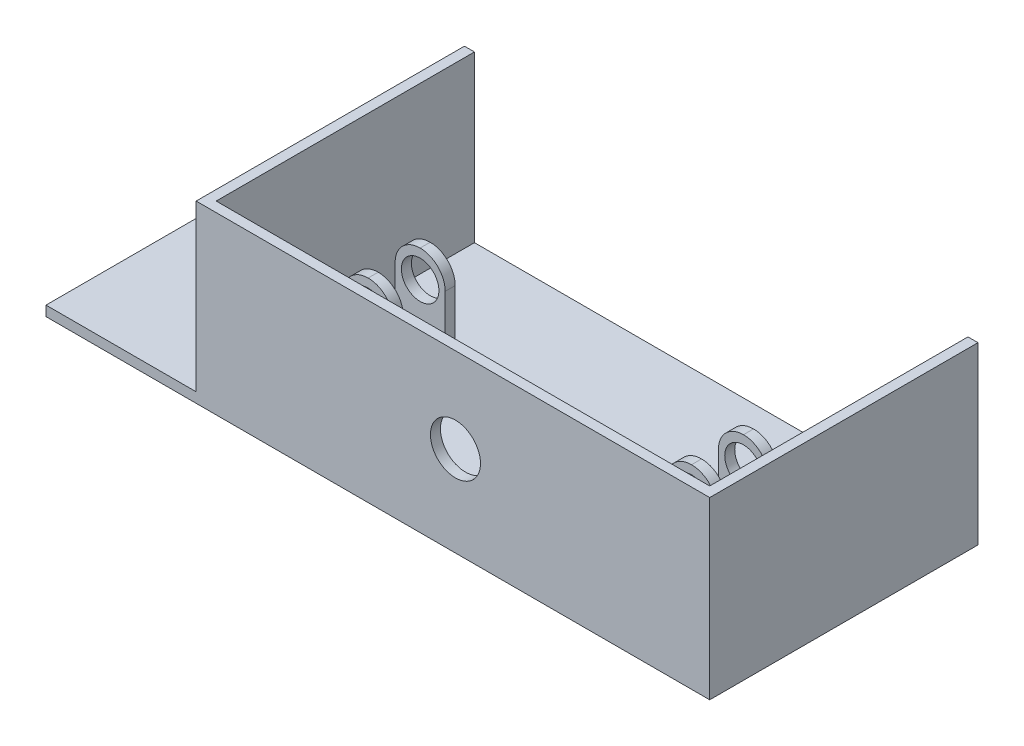
SolidWorks part; units mm, degrees
ref_plane "Plan de face" through (0, 0, 0) normal (0, 0, 1) x (1, 0, 0)
ref_plane "Plan de dessus" through (0, 0, 0) normal (0, 1, 0) x (1, 0, 0)
ref_plane "Plan de droite" through (0, 0, 0) normal (1, 0, 0) x (0, 0, -1)
sketch "Esquisse1" plane through (0, 0, 0) normal (0, 0, 1) x (1, 0, 0)
  line L1 (-17.4678, 19.1867) -> (85.1322, 19.1867)
  line L2 (-17.4678, 19.1867) -> (-17.4678, -15.8133)
  line L3 (-17.4678, -15.8133) -> (85.1322, -15.8133)
  line L4 (85.1322, 19.1867) -> (85.1322, -15.8133)
  dimension "D1" = 35
  dimension "D2" = 102.6
extrude "Boss.-Extru.1" add sketch "Esquisse1" along normal blind 53.6 and the other way blind 0.0001
sketch "Esquisse4" plane through (0, 19.1867, 0) normal (0, 1, 0) x (1, 0, 0)
  line L1 (-15.4678, -51.5999) -> (83.1322, -51.5999)
  line L2 (-15.4678, -51.5999) -> (-15.4678, 0.0001)
  line L3 (-15.4678, 0.0001) -> (83.1322, 0.0001)
  line L4 (83.1322, -51.5999) -> (83.1322, 0.0001)
  line L5 (-17.4678, -53.6) -> (-17.4678, 0.0001) construction
  line L6 (85.1322, -53.6) -> (85.1322, 0.0001) construction
  line L7 (85.1322, 0.0001) -> (-17.4678, 0.0001) construction
  dimension "D1" = 51.6
  dimension "D2" = 98.6
  dimension "D3" = 0
  dimension "D4" = 2
  dimension "D5" = 2
extrude "Enlèv. mat.-Extru.2" cut sketch "Esquisse4" against normal blind 33
sketch "Esquisse9" plane through (0, -13.8133, 0) normal (0, 1, 0) x (1, 0, 0)
  line L0 (83.1322, 0.0001) -> (-15.4678, 0.0001) construction
  line L1 (-3.4678, -25.8499) -> (6.5322, -25.8499)
  line L2 (-3.4678, -25.8499) -> (-3.4678, -27.8499)
  line L3 (-3.4678, -27.8499) -> (6.5322, -27.8499)
  line L4 (6.5322, -25.8499) -> (6.5322, -27.8499)
  line L5 (-15.4678, 0.0001) -> (-15.4678, -51.5999) construction
  line L6 (-3.4678, -36.2299) -> (6.5322, -36.2299)
  line L7 (-3.4678, -36.2299) -> (-3.4678, -38.2299)
  line L8 (-3.4678, -38.2299) -> (6.5322, -38.2299)
  line L9 (6.5322, -36.2299) -> (6.5322, -38.2299)
  line L10 (-15.4678, -51.5999) -> (83.1322, -51.5999) construction
  line L11 (61.1322, -25.8499) -> (71.1322, -25.8499)
  line L12 (61.1322, -25.8499) -> (61.1322, -27.8499)
  line L13 (61.1322, -27.8499) -> (71.1322, -27.8499)
  line L14 (71.1322, -25.8499) -> (71.1322, -27.8499)
  line L15 (61.1322, -36.2299) -> (71.1322, -36.2299)
  line L16 (61.1322, -36.2299) -> (61.1322, -38.2299)
  line L17 (61.1322, -38.2299) -> (71.1322, -38.2299)
  line L18 (71.1322, -36.2299) -> (71.1322, -38.2299)
  line L19 (83.1322, -51.5999) -> (83.1322, 0.0001) construction
  point P24 (71.1322, -37.2299)
  dimension "D1" = 25.85
  dimension "D2" = 10
  dimension "D3" = 12
  dimension "D4" = 2
  dimension "D5" = 0
  dimension "D6" = 10
  dimension "D7" = 12.38
  dimension "D8" = 2
  dimension "D9" = 13.37
  dimension "D10" = 25.85
  dimension "D11" = 2
  dimension "D12" = 2
  dimension "D13" = 10
  dimension "D14" = 10
  dimension "D15" = 12.38
  dimension "D16" = 12
  dimension "D17" = 0
extrude "Boss.-Extru.3" add sketch "Esquisse9" along normal blind 21.5
fillet "Congé2" radius 5 8 edges at (71.1322, 7.6867, 37.2299) (61.1322, 7.6867, 37.2299) (71.1322, 7.6867, 26.8499) (61.1322, 7.6867, 26.8499) (-3.4678, 7.6867, 37.2299) (6.5322, 7.6867, 37.2299) (-3.4678, 7.6867, 26.8499) (6.5322, 7.6867, 26.8499)
sketch "Esquisse10" plane through (0, 0, 25.8499) normal (0, 0, -1) x (-1, 0, 0)
  line L0 (-71.1322, -13.8133) -> (-61.1322, -13.8133) construction
  line L2 (-83.1322, -13.8133) -> (15.4678, -13.8133) construction
  line L4 (-71.1322, 2.6867) -> (-71.1322, -13.8133) construction
  line L6 (3.4678, 2.6867) -> (3.4678, -13.8133) construction
  line L7 (-83.1322, -13.8133) -> (-83.1322, 19.1867) construction
  line L8 (15.4678, -13.8133) -> (15.4678, 19.1867) construction
  circle A0 centre (-66.1322, 2.1867) radius 3.75
  circle A1 centre (-1.5322, 2.1867) radius 3.75
  point P4 (-66.1322, -13.8133)
  dimension "D1" = 7.5
  dimension "D4" = 7.5
  dimension "D2" = 16
  dimension "D3" = 5
  dimension "D5" = 16
  dimension "D6" = 5
  dimension "D7" = 64.6
  dimension "D8" = 17
  dimension "D9" = 17
extrude "Enlèv. mat.-Extru.4" cut sketch "Esquisse10" against normal blind 15
sketch "Esquisse16" plane through (-17.4678, 0, 0) normal (-1, 0, 0) x (0, 0, 1)
  line L0 (53.6, 19.1867) -> (53.6, -15.8133) construction
  line L1 (-0.0001, -15.8133) -> (53.6, -15.8133)
  line L2 (-0.0001, -15.8133) -> (-0.0001, -13.8133)
  line L3 (-0.0001, -13.8133) -> (53.6, -13.8133)
  line L4 (53.6, -15.8133) -> (53.6, -13.8133)
  dimension "D1" = 2
  dimension "D2" = 53.6001
extrude "Boss.-Extru.5" add sketch "Esquisse16" along normal blind 30
sketch "Esquisse18" plane through (0, 0, 53.6) normal (0, 0, 1) x (1, 0, 0)
  line L0 (85.1322, -15.8133) -> (85.1322, 19.1867) construction
  line L1 (-47.4678, -15.8133) -> (85.1322, -15.8133) construction
  circle A0 centre (34.3322, 2.1867) radius 5
  dimension "D1" = 50.8
  dimension "D2" = 18
extrude "Enlèv. mat.-Extru.5" cut sketch "Esquisse18" against normal blind 2.1
